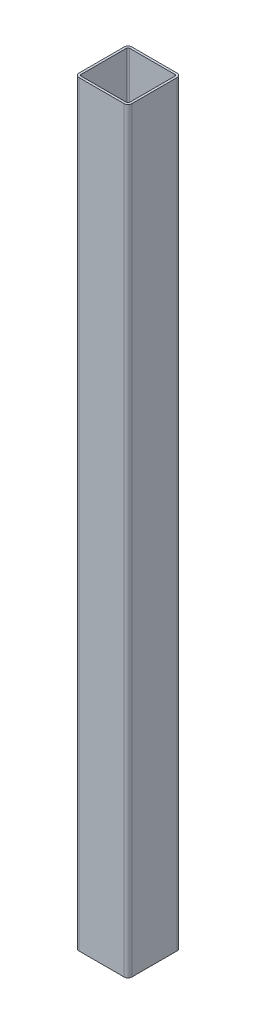
SolidWorks part; units mm, degrees
ref_plane "Спереди" through (0, 0, 0) normal (0, 0, 1) x (1, 0, 0)
ref_plane "Сверху" through (0, 0, 0) normal (0, 1, 0) x (1, 0, 0)
ref_plane "Справа" through (0, 0, 0) normal (1, 0, 0) x (0, 0, -1)
sketch "Эскиз1" plane through (0, 0, 0) normal (0, 1, 0) x (1, 0, 0)
  line L1 (-30, 35) -> (30, 35)
  line L2 (-35, 30) -> (-35, -30)
  line L3 (-30, -35) -> (30, -35)
  line L4 (35, 30) -> (35, -30)
  line L5 (-35, 35) -> (35, -35) construction
  line L6 (-35, -35) -> (35, 35) construction
  arc A0 (30, -35) -> (35, -30) centre (30, -30) ccw
  arc A1 (30, 35) -> (35, 30) centre (30, 30) cw
  arc A2 (-30, 35) -> (-35, 30) centre (-30, 30) ccw
  arc A3 (-35, -30) -> (-30, -35) centre (-30, -30) ccw
  point P0 (0, 0)
  dimension "D1" = 5
  dimension "D2" = 70
extrude "Вытянуть-Тонкостенный1" add sketch "Эскиз1" along normal blind 1000 thin thin type one direction reverse wall 3
ref_axis "Ось1" through (0, -50, 0) along (0, 1, 0)
